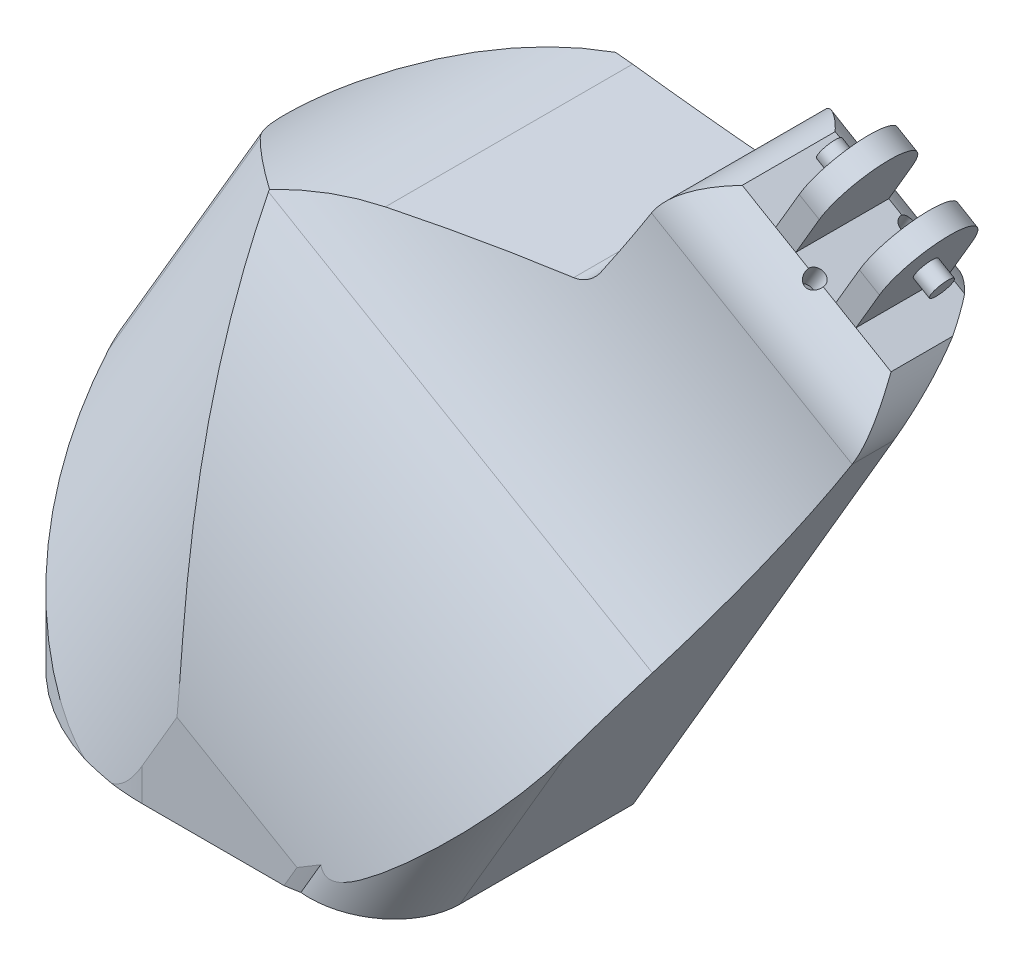
SolidWorks part; units mm, degrees
material "ABS"
ref_plane "Front Plane" through (0, 0, 0) normal (0, 0, 1) x (1, 0, 0)
ref_plane "Top Plane" through (0, 0, 0) normal (0, 1, 0) x (1, 0, 0)
ref_plane "Right Plane" through (0, 0, 0) normal (1, 0, 0) x (0, 0, -1)
sketch "Sketch1" plane through (0, 0, 0) normal (0, 0, 1) x (1, 0, 0)
  line L1 (0, 101.6) -> (101.6, 101.6)
  line L2 (0, 101.6) -> (0, 0)
  line L3 (0, 0) -> (101.6, 0)
  line L4 (101.6, 101.6) -> (101.6, 0)
  dimension "D1" = 101.6
extrude "Boss-Extrude1" add sketch "Sketch1" along normal blind 50.8
sketch "Sketch3" plane through (0, 0, 50.8) normal (0, 0, 1) x (1, 0, 0)
  line L0 (0, 0) -> (0, 20.32)
  line L1 (0, 0) -> (50.8, 0)
  line L2 (0, 0) -> (101.6, 0) construction
  line L5 (35.56, 55.88) -> (52.5466, 55.88)
  line L6 (54.8304, 57.1898) -> (58.8347, 64.0343)
  line L22 (50.8, 0) -> (80.7584, 51.2082)
  line L25 (78.2054, 60.96) -> (68.5865, 66.5874)
  arc A0 (0, 20.32) -> (35.56, 55.88) centre (35.56, 20.32) cw
  arc A1 (52.5466, 55.88) -> (54.8304, 57.1898) centre (52.5466, 58.526) ccw
  arc A2 (58.8347, 64.0343) -> (68.5865, 66.5874) centre (64.9871, 60.435) cw
  arc A3 (80.7584, 51.2082) -> (78.2054, 60.96) centre (74.606, 54.8076) ccw
  point P10 (56.8326, 60.6121)
  point P18 (0, 0)
  dimension "D1" = 60.96
  dimension "D3" = 55.88
  dimension "D4" = 20.32
  dimension "D5" = 25.4
  dimension "D8" = 50.8
extrude "Cut-Extrude1" cut sketch "Sketch3" against normal blind 69.342 flip side to cut
sketch "Sketch4" plane through (37.8466, -22.1414, 0) normal (0.8631, -0.505, 0) x (0, 0, -1)
  line L0 (0, 25.6522) -> (0, 123.9372)
  line L1 (0, 123.9372) -> (-50.8, 123.9372)
  line L2 (-50.8, 123.9372) -> (-50.8, 25.6522)
  line L4 (-14.3487, 90.9787) -> (-24.5087, 90.9787)
  line L6 (0, 84.98) -> (-50.8, 84.98) construction
  line L7 (0, 25.6522) -> (-50.8, 25.6522) construction
  line L8 (-50.8, 25.6522) -> (-50.8, 84.98) construction
  arc A1 (-28.5606, 84.98) -> (-24.5087, 90.9787) centre (-20.7316, 84.0596) cw
  arc A3 (-10.2836, 84.98) -> (-14.3487, 90.9787) centre (-17.8078, 84.2578) ccw
  arc A4 (-28.5606, 84.98) -> (-37.9355, 60.33) centre (-82.2515, 91.2921) cw
  arc A5 (-37.9355, 60.33) -> (-50.8, 25.6522) centre (22.2578, 18.2749) ccw
  arc A6 (-10.2836, 84.98) -> (-4.4444, 54.8125) centre (150.0904, 100.373) ccw
  arc A7 (-4.4444, 54.8125) -> (0, 25.6522) centre (-109.2043, 23.9268) cw
  point P19 (-38.1032, 60.0914)
  point P20 (0, 0)
  point P21 (0, 0)
  point P22 (0, 0)
  point P23 (0, 0)
  point P26 (0, 0)
  point P27 (0, 0)
  dimension "D2" = 98.285
extrude "Cut-Extrude2" cut sketch "Sketch4" against normal blind 69.342
sketch "Sketch5" plane through (0, 0, 0) normal (0, -1, 0) x (1, 0, 0)
  line L0 (50.8, 50.8) -> (50.8, 86.9289)
  line L1 (50.8, 86.9289) -> (-27.7774, 86.9289)
  line L2 (-27.7774, 86.9289) -> (-27.7774, 0)
  line L3 (-27.7774, 0) -> (25.4, 0)
  line L4 (0, 0) -> (50.8, 0) construction
  line L5 (50.8, 50.8) -> (25.4, 50.8)
  line L7 (0, 50.8) -> (0, 0) construction
  arc A0 (25.4, 50.8) -> (25.4, 0) centre (25.4, 25.4) ccw
  point P10 (26.0334, 50.5315)
extrude "Cut-Extrude7" cut sketch "Sketch5" against normal blind 152.4
ref_plane "Plane3" through (12.9534, 22.1414, 0) normal (0.505, 0.8631, 0) x (0.8631, -0.505, 0)
sketch "Sketch13" plane through (12.9534, 22.1414, 0) normal (0.505, 0.8631, 0) x (0.8631, -0.505, 0)
  line L0 (43.8475, -24.0088) -> (43.8475, -42.9577)
  line L1 (43.8475, 0) -> (43.8475, -50.8) construction
  arc A0 (43.8475, -24.0088) -> (38.7616, -15.1738) centre (6.3616, -39.7065) ccw
  arc A1 (43.8475, -42.9577) -> (35.3902, -50.5315) centre (36.2275, -42.9577) cw
  arc A3 (-10.9676, -29.3766) -> (35.3902, -50.5315) centre (26.4365, -8.7817) ccw
  arc A4 (-10.9676, -29.3766) -> (-10.9683, -18.7835) centre (-1.3468, -24.0794) cw
  arc A5 (-10.9683, -18.7835) -> (38.7616, -15.1738) centre (15.0678, -33.1143) cw
  dimension "D1" = 7.62
  dimension "D2" = 40.64
extrude "Cut-Extrude17" cut sketch "Sketch13" against normal mid plane 142.494 flip side to cut
shell "Shell5" thickness 2.54 removed face at (35.8228, 0, 34.4111)
sketch "Sketch7" plane through (45.941, 78.5273, 0) normal (0.505, 0.8631, 0) x (0.8631, -0.505, 0)
  line L0 (25.9666, -14.3487) -> (25.9666, -24.5087)
  line L1 (25.9666, -14.3487) -> (28.5066, -14.3487)
  line L2 (25.9666, -24.5087) -> (28.5066, -24.5087)
  line L3 (28.5066, -14.3487) -> (28.5066, -24.5087)
  line L4 (21.7253, -14.3487) -> (38.1136, -14.3487) construction
  line L5 (21.7253, -24.5087) -> (40.5697, -24.5087) construction
  line L6 (33.5866, -14.3487) -> (36.1266, -14.3487)
  line L7 (33.5866, -14.3487) -> (33.5866, -24.5087)
  line L8 (36.1266, -14.3487) -> (36.1266, -24.5087)
  line L9 (33.5866, -24.5087) -> (36.1266, -24.5087)
  point P8 (0, 0)
  point P11 (0, 0)
  dimension "D1" = 2.54
  dimension "D2" = 5.08
extrude "Boss-Extrude2" add sketch "Sketch7" along normal blind 10.16
sketch "Sketch8" plane through (22.4128, -13.1122, 0) normal (-0.8631, 0.505, 0) x (0, 0, 1)
  circle A0 centre (19.4287, 95.9798) radius 1.27
  dimension "D1" = 2.54
  dimension "D2" = 5.08
  dimension "D3" = 5.1588
extrude "Boss-Extrude3" add sketch "Sketch8" along normal blind 2.032
sketch "Sketch9" plane through (31.1823, -18.2427, 0) normal (0.8631, -0.505, 0) x (0, 0, -1)
  line L0 (-24.5087, 101.1387) -> (-14.3487, 101.1387) construction
  line L1 (-14.3487, 101.1387) -> (-14.3487, 90.9787) construction
  circle A0 centre (-19.4287, 96.0587) radius 1.2398
  point P4 (0, 0)
  point P6 (-14.3487, 101.1387)
  dimension "D1" = 2.4796
  dimension "D2" = 5.08
  dimension "D3" = 5.08
extrude "Boss-Extrude4" add sketch "Sketch9" along normal blind 2.032
sketch "Sketch10" plane through (31.1823, -18.2427, 0) normal (0.8631, -0.505, 0) x (0, 0, -1)
  line L0 (-24.5087, 96.0587) -> (-24.5087, 108.7409)
  line L1 (-24.5087, 101.1387) -> (-24.5087, 90.9787) construction
  line L2 (-14.3487, 96.0587) -> (-14.3487, 108.7409)
  line L3 (-14.3487, 101.1387) -> (-14.3487, 90.9787) construction
  line L4 (-14.3487, 108.7409) -> (-24.5087, 108.7409)
  arc A0 (-24.5087, 96.0587) -> (-14.3487, 96.0587) centre (-19.4287, 96.0587) cw
extrude "Cut-Extrude14" cut sketch "Sketch10" against normal blind 14.986
sketch "Sketch12" plane through (45.941, 78.5273, 0) normal (0.505, 0.8631, 0) x (0.8631, -0.505, 0)
  line L0 (28.5066, -14.3487) -> (33.5866, -14.3487) construction
  line L1 (28.5066, -24.5087) -> (33.5866, -24.5087) construction
  circle A0 centre (31.0466, -14.3487) radius 0.8983
  circle A1 centre (31.0466, -24.5087) radius 0.9342
extrude "Cut-Extrude16" cut sketch "Sketch12" against normal blind 14.986
sketch "Sketch14" plane through (0, 0, 0) normal (0, 0, 1) x (1, 0, 0)
  line L0 (52.286, 2.54) -> (50.8, 0)
  line L1 (50.8, 0) -> (0, 0)
  line L2 (0, 0) -> (0, 2.54)
  line L3 (0, 2.54) -> (52.286, 2.54)
  line L4 (50.8, 0) -> (80.7584, 51.2082) construction
  point P2 (52.9572, 4.5146)
  point P8 (0, 0)
  dimension "D1" = 2.54
  dimension "D2" = 0
extrude "Cut-Extrude18" cut sketch "Sketch14" along normal blind 112.522
